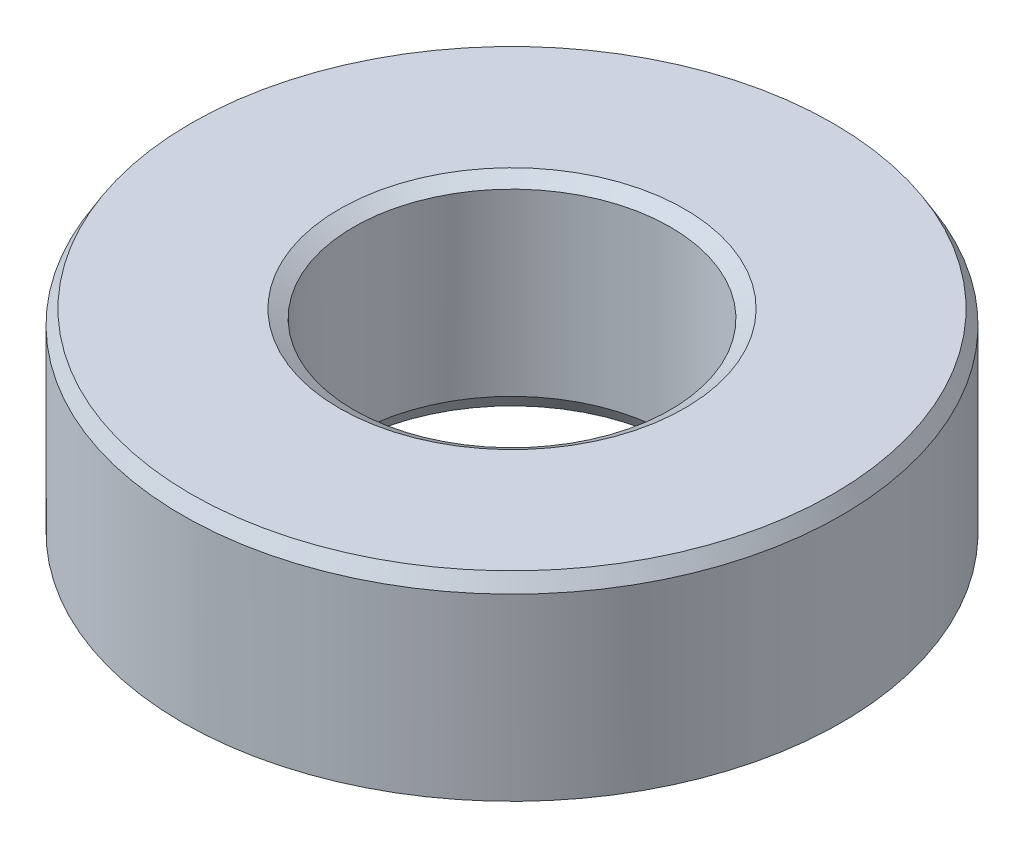
SolidWorks part; units mm, degrees
ref_plane "Front Plane" through (0, 0, 0) normal (0, 0, 1) x (1, 0, 0)
ref_plane "Top Plane" through (0, 0, 0) normal (0, 1, 0) x (1, 0, 0)
ref_plane "Right Plane" through (0, 0, 0) normal (1, 0, 0) x (0, 0, -1)
sketch "Sketch1" plane through (0, 0, 0) normal (0, 1, 0) x (1, 0, 0)
  circle A0 centre (0, 0) radius 40
  dimension "SLEEVE_OD" = 80
extrude "Boss-Extrude1" add sketch "Sketch1" along normal blind 24.5374
sketch "Sketch2" plane through (0, 0, 0) normal (0, 1, 0) x (1, 0, 0)
  circle A0 centre (0, 0) radius 19.2226
  dimension "BORE_D" = 38.4452
extrude "Cut-Extrude1" cut sketch "Sketch2" along normal through all
chamfer "Chamfer1" distance 1.7308 angle 30.682 4 edges at (0, 24.5374, 19.2226) (0, 0, 19.2226) (0, 0, 40) (0, 24.5374, 40) first distance on face at (0, 24.5374, 19.2226) first distance on face at (0, 0, 19.2226) first distance on face at (0, 24.5374, 40)
